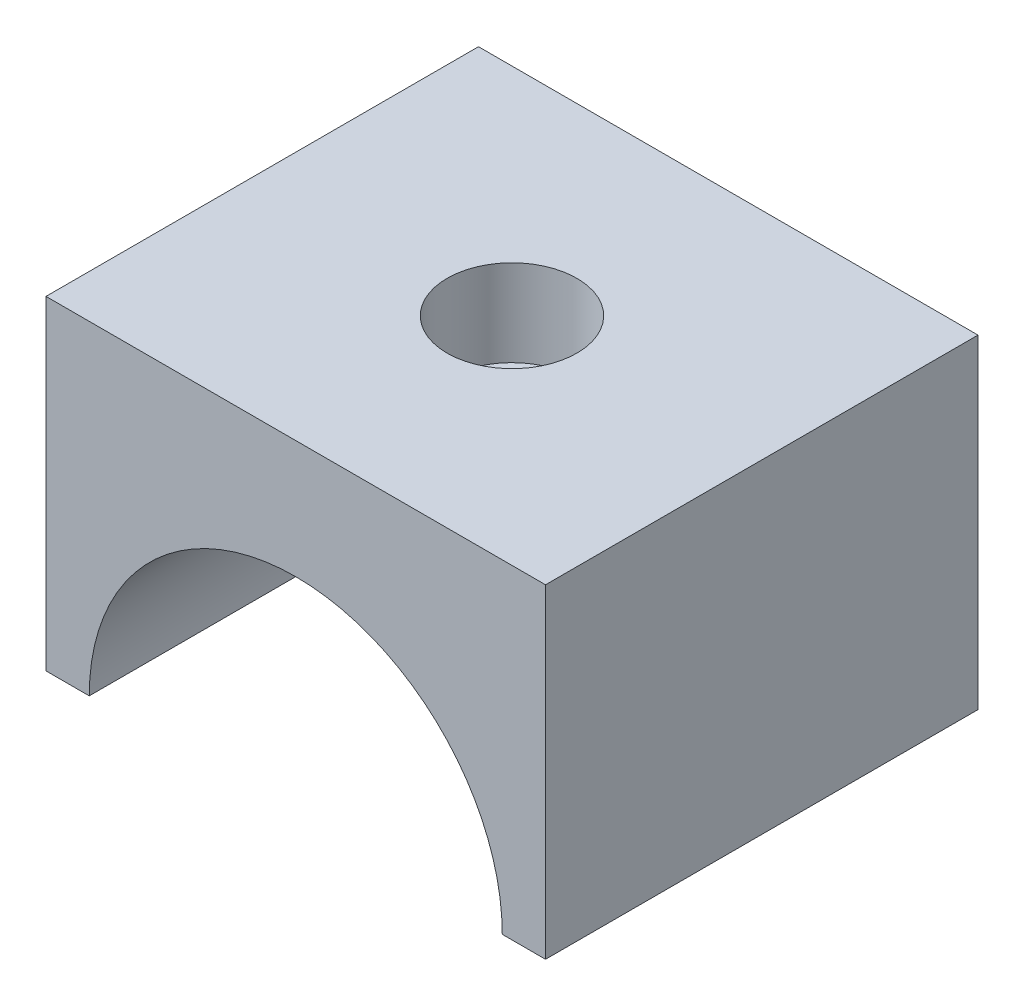
SolidWorks part; units mm, degrees
ref_plane "Front Plane" through (0, 0, 0) normal (0, 0, 1) x (1, 0, 0)
ref_plane "Top Plane" through (0, 0, 0) normal (0, 1, 0) x (1, 0, 0)
ref_plane "Right Plane" through (0, 0, 0) normal (1, 0, 0) x (0, 0, -1)
sketch "Sketch2" plane through (0, 0, 0) normal (0, 0, 1) x (1, 0, 0)
  line L0 (0, 0) -> (-2, 0)
  line L1 (-2, 0) -> (-2, 15)
  line L2 (-2, 15) -> (21.1, 15)
  line L3 (21.1, 15) -> (21.1, 0)
  line L4 (21.1, 0) -> (19.1, 0)
  arc A0 (0, 0) -> (19.1, 0) centre (9.55, 0) cw
  dimension "D1" = 9.55
  dimension "D2" = 2
  dimension "D3" = 2
  dimension "D4" = 15
extrude "Boss-Extrude1" add sketch "Sketch2" against normal blind 20
ref_plane "Plane1" through (0, 15, 0) normal (0, 1, 0) x (1, 0, 0)
sketch "Sketch3" plane through (0, 15, 0) normal (0, 1, 0) x (1, 0, 0)
  line L0 (21.1, 0) -> (-2, 0) construction
  line L1 (-2, 20) -> (-2, 0) construction
  circle A0 centre (9.55, 10) radius 1.6
  point P5 (9.55, 0)
  point P11 (-2, 10)
  dimension "D1" = 3.2
extrude "Cut-Extrude1" cut sketch "Sketch3" against normal blind 20
sketch "Sketch4" plane through (0, 15, 0) normal (0, 1, 0) x (1, 0, 0)
  circle A0 centre (9.55, 10) radius 3
extrude "Cut-Extrude2" cut sketch "Sketch4" against normal blind 4
